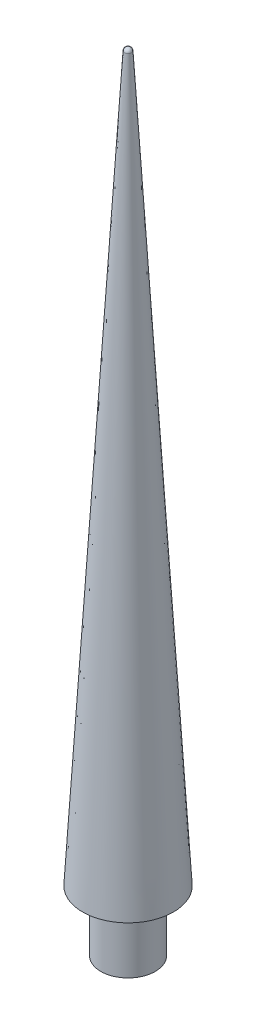
SolidWorks part; units mm, degrees
material "6061-T6 (SS)"
ref_plane "Front Plane" through (0, 0, 0) normal (0, 0, 1) x (1, 0, 0)
ref_plane "Top Plane" through (0, 0, 0) normal (0, 1, 0) x (1, 0, 0)
ref_plane "Right Plane" through (0, 0, 0) normal (1, 0, 0) x (0, 0, -1)
sketch "Sketch2" plane through (0, 0, 0) normal (0, 0, 1) x (1, 0, 0)
  line L0 (0, 0) -> (0, 164.4056) construction
  line L1 (0, 0) -> (-9.525, 0)
  line L2 (-9.525, 0) -> (0, 164.4056) construction
  line L3 (0, 164.4056) -> (0, 0) construction
  line L4 (-9.525, 0) -> (-0.7358, 151.7056)
  line L5 (0, 0) -> (0, 152.4)
  arc A0 (-0.7358, 151.7056) -> (0, 152.4) centre (0, 151.663) cw
  dimension "D1" = 152.4
  dimension "D2" = 9.525
  dimension "D3" = 12.7
revolve "Revolve1" add sketch "Sketch2" angle 360 about L0
sketch "Sketch5" plane through (0, 0, 0) normal (0, -1, 0) x (1, 0, 0)
  circle A0 centre (0, 0) radius 5.715
  dimension "D1" = 11.43
extrude "Boss-Extrude1" add sketch "Sketch5" along normal blind 12.7
hole_wizard "1/4 (0.25) Diameter Hole1" positions "Sketch6" profile "Sketch7" hole size "1/4" standard "ANSI Inch"
sketch "Sketch6" plane through (0, -12.7, 0) normal (0, -1, 0) x (1, 0, 0)
  point P0 (0, 0)
sketch "Sketch7" plane through (0, -12.7, 0) normal (1, 0, 0) x (0, 0, -1)
  line L0 (0, 0) -> (0, 40.0077)
  line L1 (0, 40.0077) -> (3.175, 38.1)
  line L2 (3.175, 38.1) -> (3.175, 0.635)
  line L3 (3.175, 0.635) -> (3.81, 0)
  line L5 (3.81, 0) -> (0, 0)
  line L6 (-3.175, 0.635) -> (-3.81, 0) construction
  line L10 (0, 40.0077) -> (-3.175, 38.1) construction
  line L11 (0, -6.35) -> (0, 107.95) construction
  dimension "Hole Dia." = 6.35
  dimension "Hole Depth" = 38.1
  dimension "Near C'Sink Dia." = 7.62
  dimension "Near C'Sink Angle" = 90
  dimension "Drill Angle" = 118
thread "Thread1" pitch 1.27 method extrude profile "Thread Profile2" start angle 0, offset 0, length 25.4, pitch 1.27, diameter 6.35
ref_plane "Plane2" through (3.175, -12.065, 0) normal (0, 0, 1) x (1, 0, 0)
sketch "Thread Profile2" plane through (3.175, -12.065, 0) normal (0, 0, 1) x (1, 0, 0)
  line L0 (0, 0) -> (0, 1.27) construction
  line L11 (0, 0) -> (0, 1.1112)
  line L12 (0, 1.1112) -> (-0.6874, 0.7144)
  line L13 (-0.6874, 0.7144) -> (-0.6874, 0.3969)
  line L15 (-0.6874, 0.3969) -> (0, 0)
  line L17 (-0.6874, 0.5556) -> (0, 0.5556) construction
  point P2 (0, 0)
  dimension "Pitch" = 1.27
  dimension "Profile_Angle" = 60
  dimension "Profile_Land" = 0.3175
  dimension "Profile_Height" = 0.6874
